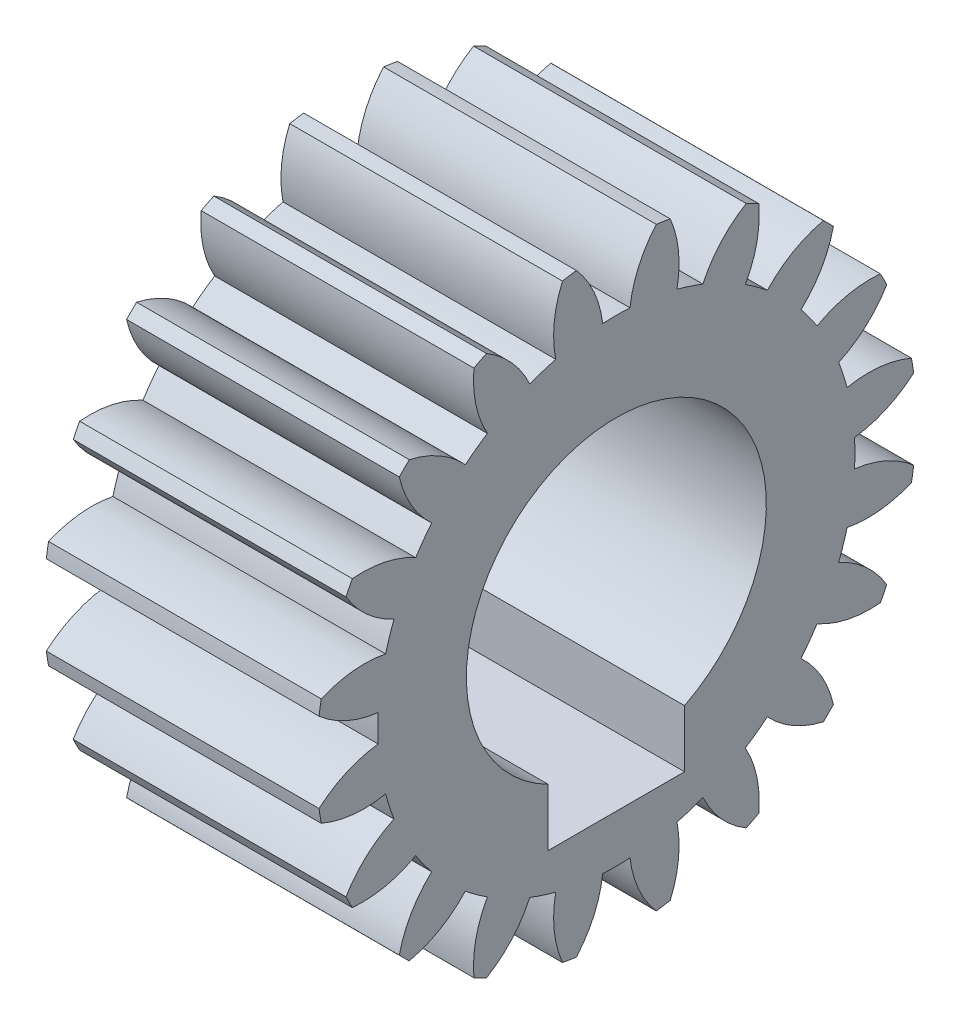
SolidWorks part; units mm, degrees
ref_plane "Plane1" through (0, 0, 0) normal (0, 0, 1) x (1, 0, 0)
ref_plane "Plane2" through (0, 0, 0) normal (0, 1, 0) x (1, 0, 0)
ref_plane "Plane3" through (0, 0, 0) normal (1, 0, 0) x (0, 0, -1)
sketch "HoldingSke" plane through (0, 0, 0) normal (0, 1, 0) x (1, 0, 0)
  line L0 (0, 0) -> (1.8794, -0.684)
  line L1 (-15, 0) -> (100, 0) construction
  line L2 (0, 0) -> (-2.1039, 2.3779)
  line L3 (0, 0) -> (-11.863, 4.5341)
  line L4 (0, 0) -> (8.1152, 2.9537)
  line L5 (0, 0) -> (-46.8476, -17.4728)
  line L6 (0, 0) -> (-4.1448, -2.7965)
  line L7 (-2.1039, 2.3779) -> (8.6586, 51.2059)
  line L8 (-76.2, 54.61) -> (-76.1, 54.61)
  line L9 (-71.009, 38.7566) -> (-53.1078, 45.2721)
  line L10 (-76.2, 71.12) -> (104.1128, 71.12)
  line L11 (0, 0) -> (-5, 0)
  line L12 (-76.2, 101.6) -> (-76.181, 101.6)
  line L13 (24.9733, 27.94) -> (52.9518, 28.4284)
  line L14 (24.9733, 27.94) -> (24.9743, 27.94)
  line L15 (24.9733, 27.94) -> (100.4006, 29.5858)
  line L16 (-63.627, -0.5) -> (-12.827, -0.5)
  circle A0 centre (0, 0) radius 0.5
  circle A1 centre (0, 0) radius 4.374
  circle A2 centre (0, 0) radius 37.5
  circle A3 centre (0, 0) radius 0.5
  dimension "MHD" = 8.748
  dimension "Hub_dia" = 75
  dimension "Bore" = 1
  dimension "MBD" = 1
  dimension "Num_teeth" = 20
  dimension "Pitch" = 2
  dimension "Overall_len" = 50
  dimension "Show_teeth" = 20
  dimension "Thickness" = 5
  dimension "OAL" = 50.0001
  dimension "T_dim" = 0.1
  dimension "Ap" = 20
  dimension "H" = 19.05
  dimension "Pitch_radius" = 180.3128
  dimension "Width" = 5
  dimension "Backlash" = 0.019
  dimension "Addendum_fac" = 1
  dimension "Dedendum_fac" = 1.25
  dimension "Clearance_fac" = 0.25
  dimension "Dedendum_add" = 0.001
  dimension "Module" = 0.5
sketch "BasProSke" plane through (0, 0, 0) normal (0, 1, 0) x (1, 0, 0)
  line L0 (-10, 0) -> (60, 0) construction
  line L1 (0, 0) -> (0, 5.5)
  line L2 (0, 0) -> (5, 0)
  line L3 (5, 0) -> (5, 5.5)
  line L4 (5, 5.5) -> (0, 5.5)
  dimension "Thickness" = 5
  dimension "Diameter" = 11
revolve "Base-Revolve" add sketch "BasProSke" angle 360 about L0
sketch "TooCutSke" plane through (0, 0, 0) normal (1, 0, 0) x (0, 0, -1)
  line L1 (0, 0) -> (0, 107) construction
  line L2 (0, 0) -> (-0.4255, 4.9819) construction
  line L3 (0, 0) -> (-1.5603, 9.8514) construction
  line L4 (-0.4255, 4.9819) -> (-0.7802, 4.9257) construction
  arc A0 (0.2499, 4.3669) -> (-0.2499, 4.3669) centre (0, 0) ccw
  arc A1 (0.7528, 5.4739) -> (-0.7528, 5.4739) centre (0, 0) ccw
  circle A2 centre (0, 0) radius 5 construction
  circle A3 centre (0, 0) radius 4.6985 construction
  arc A4 (-0.2499, 4.3669) -> (-0.7528, 5.4739) centre (-2.2361, 4.1322) ccw
  arc A5 (0.7528, 5.4739) -> (0.2499, 4.3669) centre (2.2361, 4.1322) ccw
  dimension "Root_dia" = 8.748
  dimension "Overcut_dia" = 11.0508
  dimension "Pitch_dia" = 10
  dimension "Base_dia" = 9.3969
  dimension "Flank_rad" = 2
  dimension "Half_ang" = 9
  dimension "Half_CT" = 0.359
extrude "ToothCut" cut sketch "TooCutSke" along normal through all
fillet "Breaks" [suppressed] radius 0.01 tangent propagation no
fillet "RootFillets" [suppressed] radius 0.126
pattern_circular "TeethCuts" count 20 every 18 about axis through (-10, 0, 0) along (1, 0, 0) of "ToothCut", "RootFillets", "Breaks"
sketch "HubNeaOneSke" plane through (0, 0, 0) normal (-1, 0, 0) x (0, 0, 1)
  circle A0 centre (0, 0) radius 4.374
  dimension "Diameter" = 8.748
extrude "HubNearOne" [suppressed] add sketch "HubNeaOneSke" along normal blind 45.0001
sketch "HubNeaBotSke" plane through (0, 0, 0) normal (-1, 0, 0) x (0, 0, 1)
  circle A0 centre (0, 0) radius 4.374
  dimension "Diameter" = 8.748
extrude "HubNearBoth" [suppressed] add sketch "HubNeaBotSke" along normal blind 22.5
ref_plane "FarPln" through (5, 0, 0) normal (1, 0, 0) x (0, 0, -1)
sketch "HubFarSke" plane through (5, 0, 0) normal (1, 0, 0) x (0, 0, -1)
  circle A0 centre (0, 0) radius 4.374
  dimension "Diameter" = 8.748
extrude "HubFar" [suppressed] add sketch "HubFarSke" along normal blind 22.5
sketch "BorSke" plane through (0, 0, 0) normal (1, 0, 0) x (0, 0, -1)
  circle A0 centre (0, 0) radius 0.5
  dimension "Diameter" = 1
extrude "Bore" cut sketch "BorSke" along normal mid plane 100.0001
sketch "KeySke" plane through (0, 0, 0) normal (1, 0, 0) x (0, 0, -1)
  line L0 (-0.05, 0) -> (-0.05, 0.6)
  line L1 (-0.05, 0.6) -> (0.05, 0.6)
  line L2 (0.05, 0.6) -> (0.05, 0)
  line L3 (0, 0) -> (0, 34) construction
  line L4 (-0.05, 0) -> (0.05, 0)
  dimension "Offset" = 0.6
  dimension "Width" = 0.1
extrude "Keyway" [suppressed] cut sketch "KeySke" along normal mid plane 100.0001
pattern_circular "Keyway2" [suppressed] count 2 every 90 about axis through (-10, 0, 0) along (1, 0, 0) reverse direction yes
sketch "Sketch1" plane through (5, 0, 0) normal (1, 0, 0) x (0, 0, -1)
  line L0 (0, 0) -> (0, -8.1441) construction
  line L1 (-1.25, -1.7594) -> (-1.25, -3.5)
  line L2 (-1.25, -1.7594) -> (1.25, -1.7594)
  line L3 (-1.25, -3.5) -> (1.25, -3.5)
  line L4 (1.25, -1.7594) -> (1.25, -3.5)
  line L5 (0, -3.5) -> (0, -1.7594) construction
  line L6 (-1.25, -2.6297) -> (1.25, -2.6297) construction
  circle A0 centre (0, 0) radius 2.75
  point P3 (0, -2.75)
  point P6 (0, -2.6297)
  dimension "D1" = 5.5
  dimension "D2" = 3.5
  dimension "D3" = 2.5
extrude "Cut-Extrude1" cut sketch "Sketch1" against normal through all both and the other way through all contours L4 A0 L1 L2 | A0 L1 L3 L4 | L1 A0 L4 L2 region at (5, -2.2102, 0) region at (5, 0.2292, 0) region at (5, -3.0714, 0)
equation "' \"Module@HoldingSke\" = 6.35"
equation "' \"Num_teeth@HoldingSke\" = 12"
equation "' \"Ap@HoldingSke\" =  20"
equation "' \"Ap@HoldingSke\" = 20"
equation "' \"Width@HoldingSke\" = 0.5 * 25.4"
equation "' \"Hub_dia@HoldingSke\"= 1 * 25.4"
equation "' \"Hub_dia@HoldingSke\" = 1 * 25.4"
equation "' \"Overall_len@HoldingSke\" = 1.0 * 25.4"
equation "' \"Bore@HoldingSke\" = 0.75 * 25.4"
equation "' \"T_dim@HoldingSke\" = 0.1 * 25.4"
equation "' \"Width@KeySke\" = 0.25 * 25.4"
equation "' \"Show_teeth@HoldingSke\" = 13"
equation "' \"Backlash@HoldingSke\" = 0.009 * 25.4"
equation "' \"Addendum_fac@HoldingSke\" = 1.0"
equation "' \"Dedendum_fac@HoldingSke\" = 1.25"
equation "' \"Dedendum_add@HoldingSke\" = 0.00005 * 25.4"
equation "' \"Clearance_fac@HoldingSke\" = 0.25"
equation "\"Pitch@HoldingSke\" = 1 / \"Module@HoldingSke\""
equation "\"Overcut_dia@TooCutSke\" = (\"Num_teeth@HoldingSke\" + 2 * \"Addendum_fac@HoldingSke\") / \"Pitch@HoldingSke\" + 0.002 * 25.4"
equation "\"Pitch_dia@TooCutSke\" = \"Num_teeth@HoldingSke\" / \"Pitch@HoldingSke\""
equation "\"Base_dia@TooCutSke\" = \"Num_teeth@HoldingSke\" / \"Pitch@HoldingSke\" * cos((\"Ap@HoldingSke\"  * 3.14159265 / 180))"
equation "\"Root_dia@TooCutSke\" = (\"Num_teeth@HoldingSke\" + 2) / \"Pitch@HoldingSke\" - 2 * (\"Addendum_fac@HoldingSke\" + \"Dedendum_fac@HoldingSke\") / \"Pitch@HoldingSke\" - \"Dedendum_add@HoldingSke\" * 2"
equation "\"Half_ang@TooCutSke\" = 180 / \"Num_teeth@HoldingSke\""
equation "\"Half_CT@TooCutSke\" = \"Num_teeth@HoldingSke\" / \"Pitch@HoldingSke\" * sin((3.14159265 / 2 / \"Num_teeth@HoldingSke\")) / 2 - 7 * \"Backlash@HoldingSke\" / 4"
equation "\"Flank_rad@TooCutSke\" = \"Num_teeth@HoldingSke\" / \"Pitch@HoldingSke\" / 5"
equation "\"Radius@RootFillets\" = \"Clearance_fac@HoldingSke\" / \"Pitch@HoldingSke\" + \"Dedendum_add@HoldingSke\""
equation "\"Break_rad@Breaks\" = 0.02 / \"Pitch@HoldingSke\""
equation "\"Thickness@HoldingSke\" = \"Width@HoldingSke\""
equation "\"OAL@HoldingSke\" = \"Thickness@HoldingSke\""
equation "\"MHD@HoldingSke\" = (\"Num_teeth@HoldingSke\" + 2) / \"Pitch@HoldingSke\" - 2 * (\"Addendum_fac@HoldingSke\" + \"Dedendum_fac@HoldingSke\")  / \"Pitch@HoldingSke\" - \"Dedendum_add@HoldingSke\" * 2"
equation "\"MBD@HoldingSke\" = (\"Num_teeth@HoldingSke\" + 2) / \"Pitch@HoldingSke\" - 2 * (\"Addendum_fac@HoldingSke\" + \"Dedendum_fac@HoldingSke\")  / \"Pitch@HoldingSke\" - \"Dedendum_add@HoldingSke\" * 2 - 0.002 * 25.4"
equation "\"MHD@HoldingSke\" = ((sgn( \"MHD@HoldingSke\" - \"Hub_dia@HoldingSke\" )-1)*( \"MHD@HoldingSke\" - \"Hub_dia@HoldingSke\" ))/-2+ \"Hub_dia@HoldingSke\""
equation "\"MBD@HoldingSke\" = ((sgn( \"MBD@HoldingSke\" - \"Bore@HoldingSke\" )-1)*( \"MBD@HoldingSke\" - \"Bore@HoldingSke\" ))/-2+ \"Bore@HoldingSke\""
equation "\"OAL@HoldingSke\" = ((sgn( \"OAL@HoldingSke\" - \"Overall_len@HoldingSke\" )+1)*( \"OAL@HoldingSke\" - \"Overall_len@HoldingSke\" ))/2 + \"Overall_len@HoldingSke\" + 0.000002 * 25.4"
equation "\"Num_teeth@TeethCuts\" = int( \"Show_teeth@HoldingSke\" ) + 1"
equation "\"Num_teeth@TeethCuts\" = ((sgn( \"Num_teeth@TeethCuts\" - \"Num_teeth@HoldingSke\" )-1)*( \"Num_teeth@TeethCuts\" - \"Num_teeth@HoldingSke\" ))/-2+ \"Num_teeth@HoldingSke\""
equation "\"Num_teeth@TeethCuts\" = ((sgn( \"Num_teeth@TeethCuts\" - 2.0)+1)*( \"Num_teeth@TeethCuts\" - 2.0))/2 +2.0"
equation "\"Angle@TeethCuts\" = 360.0 / \"Num_teeth@HoldingSke\""
equation "\"Diameter@BasProSke\" = (\"Num_teeth@HoldingSke\" + 2 * \"Addendum_fac@HoldingSke\") / \"Pitch@HoldingSke\""
equation "\"Thickness@BasProSke\"  = \"Thickness@HoldingSke\""
equation "' \"Fillet_rad@BasProSke\" =  \"Thickness@HoldingSke\" * 0.05"
equation "' \"Fillet_rad@BasProSke\" = \"Thickness@HoldingSke\" * 0.05"
equation "\"MHD@HoldingSke\" = ((sgn( \"MHD@HoldingSke\" - \"Root_dia@TooCutSke\" )-1)*( \"MHD@HoldingSke\" - \"Root_dia@TooCutSke\" ))/-2+ \"Root_dia@TooCutSke\""
equation "\"Diameter@HubNeaOneSke\" = \"MHD@HoldingSke\""
equation "\"Length@HubNearOne\" = \"OAL@HoldingSke\" - \"Thickness@BasProSke\""
equation "\"Diameter@HubNeaBotSke\" = \"MHD@HoldingSke\""
equation "\"Length@HubNearBoth\" = ( \"OAL@HoldingSke\" - \"Thickness@BasProSke\" ) / 2.0"
equation "\"Thickness@FarPln\" = \"Thickness@BasProSke\""
equation "\"Diameter@HubFarSke\" = \"MHD@HoldingSke\""
equation "\"Length@HubFar\" = ( \"OAL@HoldingSke\" - \"Thickness@BasProSke\" ) / 2.0"
equation "\"Diameter@BorSke\" = \"MBD@HoldingSke\""
equation "\"D1@Bore\" = \"OAL@HoldingSke\" * 2.0"
equation "\"D1@Keyway\" = \"OAL@HoldingSke\" * 2.0"
equation "\"Offset@KeySke\" = \"T_dim@HoldingSke\" + \"MBD@HoldingSke\" / 2.0"
